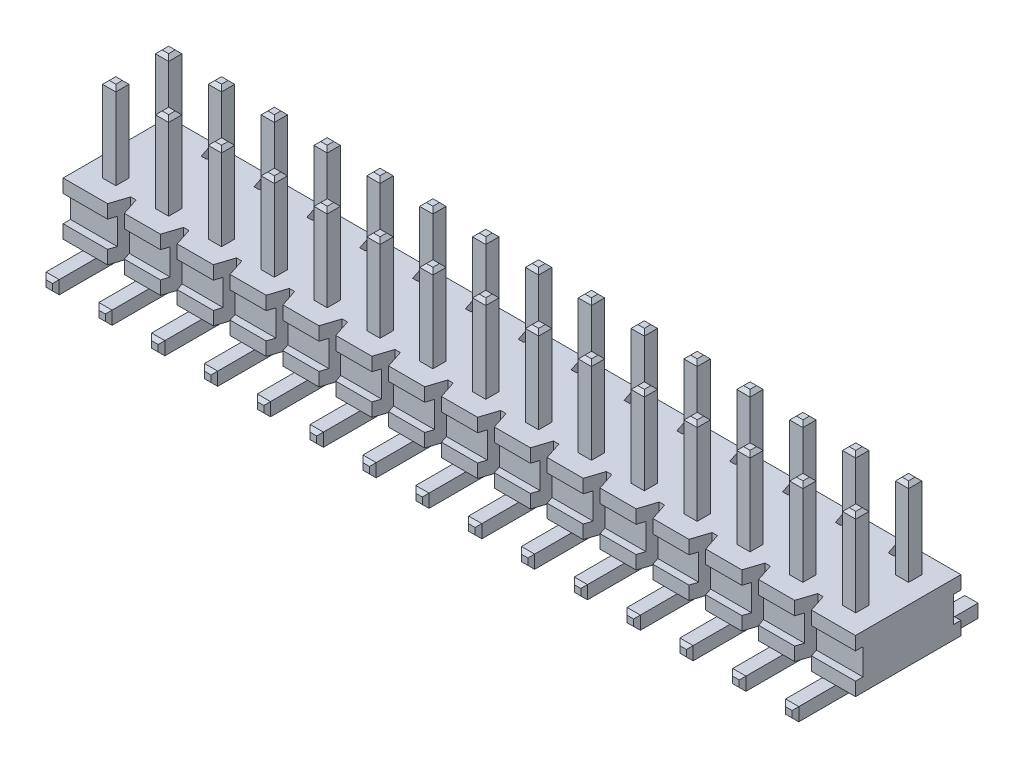
SolidWorks part; units mm, degrees
ref_plane "Front Plane" through (0, 0, 0) normal (0, 0, 1) x (1, 0, 0)
ref_plane "Top Plane" through (0, 0, 0) normal (0, 1, 0) x (1, 0, 0)
ref_plane "Right Plane" through (0, 0, 0) normal (1, 0, 0) x (0, 0, -1)
sketch "Sketch1" plane through (0, 0, 0) normal (0, 1, 0) x (1, 0, 0)
  line L0 (-14.9924, -1.9939) -> (14.9924, 1.9939) construction
  line L1 (-14.9924, 1.9939) -> (14.9924, 1.9939)
  line L2 (-14.9924, 1.9939) -> (-14.9924, -1.9939)
  line L3 (-14.9924, -1.9939) -> (14.9924, -1.9939)
  line L4 (14.9924, 1.9939) -> (14.9924, -1.9939)
  dimension "D1" = 3.9878
  dimension "D2" = 29.9847
extrude "Body" add sketch "Sketch1" along normal mid plane 2.0066
sketch "Sketch3" plane through (0, 1.0033, 0) normal (0, 1, 0) x (1, 0, 0)
  line L0 (-13.3099, 1.9939) -> (-12.6749, 1.9939)
  line L1 (14.9924, 1.9939) -> (-14.9924, 1.9939) construction
  line L2 (-12.6749, 1.9939) -> (-12.8908, 1.3335)
  line L3 (-12.8908, 1.3335) -> (-13.094, 1.3335)
  line L4 (-13.094, 1.3335) -> (-13.3099, 1.9939)
  line L5 (-12.9924, 1.3335) -> (-12.9924, 1.9939) construction
  line L6 (-14.9924, 1.9939) -> (-14.9924, -1.9939) construction
  line L7 (0, 0) -> (-14.9924, 0) construction
  line L8 (-13.094, -1.3335) -> (-13.3099, -1.9939)
  line L9 (-12.8908, -1.3335) -> (-13.094, -1.3335)
  line L10 (-12.6749, -1.9939) -> (-12.8908, -1.3335)
  line L11 (-13.3099, -1.9939) -> (-12.6749, -1.9939)
  dimension "D1" = 0.635
  dimension "D2" = 0.2032
  dimension "D3" = 0.6604
  dimension "D4" = 2
extrude "In-Between Cores" cut sketch "Sketch3" against normal through all
sketch "Sketch4" plane through (-14.9924, 0, 0) normal (-1, 0, 0) x (0, 0, 1)
  line L0 (-1.9939, 1.0033) -> (-1.9939, -1.0033) construction
  line L1 (-1.9939, 0.4953) -> (-1.7145, 0.4953)
  line L2 (-1.9939, 0.4953) -> (-1.9939, -0.4953)
  line L3 (-1.9939, -0.4953) -> (-1.7145, -0.4953)
  line L4 (-1.7145, 0.4953) -> (-1.7145, -0.4953)
  line L5 (1.9939, 1.0033) -> (1.9939, -1.0033) construction
  line L6 (1.9939, 0.4953) -> (1.7145, 0.4953)
  line L7 (1.9939, 0.4953) -> (1.9939, -0.4953)
  line L8 (1.9939, -0.4953) -> (1.7145, -0.4953)
  line L9 (1.7145, 0.4953) -> (1.7145, -0.4953)
  line L10 (-1.9939, 1.0033) -> (1.9939, 1.0033) construction
  line L11 (-1.9939, -1.0033) -> (1.9939, -1.0033) construction
  dimension "D1" = 0.2794
  dimension "D2" = 0.508
  dimension "D3" = 0.508
extrude "Side Cut" cut sketch "Sketch4" against normal through all
sketch "Sketch5" plane through (0, 1.0033, 0) normal (0, 1, 0) x (1, 0, 0)
  line L0 (-13.9924, -1.2502) -> (-13.9924, -0.7498) construction
  line L1 (-14.2425, -0.7498) -> (-13.7422, -0.7498)
  line L2 (-14.2425, -0.7498) -> (-14.2425, -1.2502)
  line L3 (-14.2425, -1.2502) -> (-13.7422, -1.2502)
  line L4 (-13.7422, -0.7498) -> (-13.7422, -1.2502)
  line L5 (-13.7422, -1) -> (-14.2425, -1) construction
  line L6 (-14.9924, 1.9939) -> (-14.9924, -1.9939) construction
  line L7 (-14.9924, -1.9939) -> (-13.3099, -1.9939) construction
  dimension "D1" = 0.5004
  dimension "D2" = 1
  dimension "D3" = 0.9939
extrude "Contact" add sketch "Sketch5" along normal blind 3.2004
chamfer "Contact Chamfer" distance 0.127 angle 45 4 edges at (-13.9923, 4.2037, 0.7498) (-13.7422, 4.2037, 1) (-13.9923, 4.2037, 1.2502) (-14.2425, 4.2037, 1)
pattern_linear "Contact Pattern" count 15 spacing 2 along (1, 0, 0) count 2 spacing 2 along (0, 0, -1) of "Contact", "Contact Chamfer"
pattern_linear "Inbetween Pattern" count 14 spacing 2 along (1, 0, 0) of "In-Between Cores"
sketch "Sketch7" plane through (0, 0, 0) normal (1, 0, 0) x (0, 0, -1)
  line L0 (-3.175, 6.3373) -> (3.175, 6.3373)
  line L1 (-3.175, 6.3373) -> (-3.175, 5.0673)
  line L2 (-3.175, 5.0673) -> (-2.3876, 5.0673)
  line L3 (-2.0828, 4.7625) -> (-2.0828, 1.3081)
  line L4 (-1.778, 1.0033) -> (-1.7526, 1.0033)
  line L5 (-1.4478, 1.3081) -> (-1.4478, 1.3843)
  line L6 (-1.4478, 1.3843) -> (-1.2192, 1.6129)
  line L7 (-1.2192, 1.6129) -> (-1.2192, 1.9177)
  line L8 (-1.2192, 1.9177) -> (-1.4478, 2.3136)
  line L9 (-1.4478, 2.3136) -> (-1.4478, 4.7625)
  line L10 (-1.143, 5.0673) -> (-0.8763, 5.0673)
  line L11 (-0.5715, 4.7625) -> (-0.5715, 2.3136)
  line L12 (-0.5715, 2.3136) -> (-0.6985, 1.9177)
  line L13 (-0.6985, 1.9177) -> (-0.6985, 1.6129)
  line L14 (-0.6985, 1.6129) -> (-0.5279, 1.3175)
  line L15 (0, 0) -> (0, 6.3373) construction
  line L16 (-1.2192, 1.7653) -> (-2.0828, 1.7653) construction
  line L17 (-1.9939, 1.0033) -> (1.9939, 1.0033) construction
  line L18 (0.6985, 1.6129) -> (0.5279, 1.3175)
  line L19 (0.6985, 1.9177) -> (0.6985, 1.6129)
  line L20 (0.5715, 2.3136) -> (0.6985, 1.9177)
  line L21 (0.5715, 4.7625) -> (0.5715, 2.3136)
  line L22 (1.143, 5.0673) -> (0.8763, 5.0673)
  line L23 (1.4478, 2.3136) -> (1.4478, 4.7625)
  line L24 (1.2192, 1.9177) -> (1.4478, 2.3136)
  line L25 (1.2192, 1.6129) -> (1.2192, 1.9177)
  line L26 (1.4478, 1.3843) -> (1.2192, 1.6129)
  line L27 (1.4478, 1.3081) -> (1.4478, 1.3843)
  line L28 (1.778, 1.0033) -> (1.7526, 1.0033)
  line L29 (2.0828, 4.7625) -> (2.0828, 1.3081)
  line L30 (3.175, 5.0673) -> (2.3876, 5.0673)
  line L31 (3.175, 6.3373) -> (3.175, 5.0673)
  arc A0 (-0.5279, 1.3175) -> (0.5279, 1.3175) centre (0, 1.6223) ccw
  arc A1 (-2.3876, 5.0673) -> (-2.0828, 4.7625) centre (-2.3876, 4.7625) cw
  arc A2 (-2.0828, 1.3081) -> (-1.778, 1.0033) centre (-1.778, 1.3081) ccw
  arc A3 (-1.7526, 1.0033) -> (-1.4478, 1.3081) centre (-1.7526, 1.3081) ccw
  arc A4 (-1.4478, 4.7625) -> (-1.143, 5.0673) centre (-1.143, 4.7625) cw
  arc A5 (-0.8763, 5.0673) -> (-0.5715, 4.7625) centre (-0.8763, 4.7625) cw
  arc A6 (0.8763, 5.0673) -> (0.5715, 4.7625) centre (0.8763, 4.7625) ccw
  arc A7 (1.4478, 4.7625) -> (1.143, 5.0673) centre (1.143, 4.7625) ccw
  arc A8 (1.7526, 1.0033) -> (1.4478, 1.3081) centre (1.7526, 1.3081) cw
  arc A9 (2.0828, 1.3081) -> (1.778, 1.0033) centre (1.778, 1.3081) cw
  arc A10 (2.3876, 5.0673) -> (2.0828, 4.7625) centre (2.3876, 4.7625) ccw
  dimension "D12" = 1.2192
  dimension "D14" = 0.3048
  dimension "D1" = 3.175
  dimension "D2" = 1.0922
  dimension "D3" = 0.635
  dimension "D4" = 0.2286
  dimension "D5" = 1.27
  dimension "D6" = 5.334
  dimension "D7" = 45
  dimension "D8" = 0.3048
  dimension "D9" = 0.762
  dimension "D10" = 0.6985
  dimension "D11" = 0.127
  dimension "D13" = 30
sketch "Sketch6" plane through (-14.2425, 0, 0) normal (-1, 0, 0) x (0, 0, 1)
  line L0 (-1.2502, -1.0033) -> (-3.5179, -1.0033)
  line L1 (-1.9939, -1.0033) -> (1.9939, -1.0033) construction
  line L2 (-3.5179, -1.0033) -> (-3.5179, -1.5037)
  line L3 (-3.5179, -1.5037) -> (-1.2502, -1.5037)
  line L4 (-1.2502, -1.0033) -> (-0.7498, -1.0033)
  line L5 (0, 0) -> (0, -2.839) construction
  line L6 (1.2502, -1.0033) -> (0.7498, -1.0033)
  line L7 (3.5179, -1.5037) -> (1.2502, -1.5037)
  line L8 (3.5179, -1.0033) -> (3.5179, -1.5037)
  line L9 (1.2502, -1.0033) -> (3.5179, -1.0033)
  arc A0 (-1.2502, -1.5037) -> (-0.7498, -1.0033) centre (-1.2502, -1.0033) ccw
  arc A1 (1.2502, -1.5037) -> (0.7498, -1.0033) centre (1.2502, -1.0033) cw
  dimension "D1" = 7.0358
  dimension "D2" = 0.5004
extrude "SM" add sketch "Sketch6" against normal blind 0.5004
chamfer "SM Chamfer" distance 0.127 angle 45 8 edges at (-13.9924, -1.0033, 3.5179) (-13.7422, -1.2535, 3.5179) (-13.9924, -1.5037, 3.5179) (-14.2425, -1.2535, 3.5179) (-13.9923, -1.5037, -3.5179) (-13.7422, -1.2535, -3.5179) (-13.9923, -1.0033, -3.5179) (-14.2425, -1.2535, -3.5179)
pattern_linear "SM Pattern" count 15 spacing 1.999 along (1, 0, 0) of "SM", "SM Chamfer"
sketch "Sketch8" plane through (-14.2425, 0, 0) normal (-1, 0, 0) x (0, 0, 1)
  line L0 (1.2502, -1.0033) -> (1.2502, -1.5227)
  line L1 (-1.9939, -1.0033) -> (1.9939, -1.0033) construction
  line L2 (1.2502, -1.0033) -> (0.7498, -1.0033)
  line L3 (0.7498, -1.0033) -> (0.7498, -1.5227)
  line L4 (-0.7498, -1.0033) -> (-1.2502, -1.0033)
  line L5 (-1.2502, -1.0033) -> (-1.2502, -3.5227)
  line L6 (-0.7498, -1.0033) -> (-0.7498, -3.5227)
  line L7 (1.7506, -2.0231) -> (4.5339, -2.0231)
  line L8 (1.7506, -2.5235) -> (4.5339, -2.5235)
  line L9 (4.5339, -2.5235) -> (4.5339, -2.0231)
  line L10 (-0.2494, -4.0231) -> (4.5339, -4.0231)
  line L11 (-0.2494, -4.5235) -> (4.5339, -4.5235)
  line L12 (4.5339, -4.5235) -> (4.5339, -4.0231)
  line L13 (4.5339, -2.2733) -> (0, -2.2733) construction
  line L14 (4.5339, -4.2733) -> (0, -4.2733) construction
  line L15 (1.9939, -0.4953) -> (1.9939, -1.0033) construction
  line L16 (1, 1.0033) -> (1, -1.0033) construction
  line L17 (0.7498, 1.0033) -> (1.2502, 1.0033) construction
  line L18 (-1, 1.0033) -> (-1, -1.0033) construction
  arc A0 (1.2502, -1.5227) -> (1.7506, -2.0231) centre (1.7506, -1.5227) ccw
  arc A1 (0.7498, -1.5227) -> (1.7506, -2.5235) centre (1.7506, -1.5227) ccw
  arc A2 (-0.7498, -3.5227) -> (-0.2494, -4.0231) centre (-0.2494, -3.5227) ccw
  arc A3 (-1.2502, -3.5227) -> (-0.2494, -4.5235) centre (-0.2494, -3.5227) ccw
  dimension "D1" = 0.5004
  dimension "D2" = 0.5004
  dimension "D7" = 0.5004
  dimension "D3" = 1.27
  dimension "D4" = 2
  dimension "D5" = 0.5004
  dimension "D6" = 2.54
  dimension "D8" = 2
sketch "Sketch10" plane through (-14.2425, 0, 0) normal (-1, 0, 0) x (0, 0, 1)
  line L1 (0.7498, -1.0033) -> (1.2502, -1.0033)
  line L2 (0.7498, -1.0033) -> (0.7498, -3.4671)
  line L3 (0.7498, -3.4671) -> (1.2502, -3.4671)
  line L4 (1.2502, -1.0033) -> (1.2502, -3.4671)
  line L5 (1, -1.0033) -> (1, 1.0033) construction
  line L6 (0.7498, 1.0033) -> (1.2502, 1.0033) construction
  line L7 (-1.9939, -1.0033) -> (1.9939, -1.0033) construction
  dimension "D1" = 0.5004
  dimension "D2" = 2.4638
ref_plane "LC Plane" through (-12.9954, 0, 0) normal (1, 0, 0) x (0, 0, -1)
ref_plane "Shroud Plane" through (0, 4.3307, 0) normal (0, 1, 0) x (-1, 0, 0)
ref_plane "AP Plane" through (-12.9924, 0, 0) normal (-1, 0, 0) x (0, 0, 1)
sketch "Sketch11" plane through (-12.9924, 0, 0) normal (1, 0, 0) x (0, 0, -1)
  line L0 (-0.5461, -0.7493) -> (-0.5461, -2.6543)
  line L1 (-1.9939, -1.0033) -> (1.9939, -1.0033) construction
  line L2 (-0.5461, -2.6543) -> (-0.4191, -2.9083)
  line L3 (1.9939, -1.0033) -> (-1.9939, -1.0033) construction
  line L4 (-0.4191, -2.9083) -> (0, -2.9083)
  line L5 (-0.5461, -0.7493) -> (0, -0.7493)
  line L6 (0, -0.7493) -> (0, -2.9083)
  line L7 (0, -0.7493) -> (0, 0) construction
  dimension "D1" = 0.254
  dimension "D2" = 1.905
  dimension "D3" = 0.254
  dimension "D4" = 0.5461
  dimension "D5" = 0.127
sketch "Sketch12" plane through (-12.9954, 0, 0) normal (1, 0, 0) x (0, 0, -1)
  line L0 (-0.5778, -0.8001) -> (-0.5778, -1.61)
  line L1 (-0.5778, -1.61) -> (-0.7112, -1.61)
  line L2 (-0.7112, -1.61) -> (-0.5778, -1.841)
  line L3 (-0.5778, -1.841) -> (-0.5778, -1.8894)
  line L4 (-0.5778, -1.8894) -> (-0.7112, -1.8894)
  line L5 (-0.7112, -1.8894) -> (-0.3429, -2.5273)
  line L6 (-0.2159, -2.5273) -> (-0.2159, -1.3843)
  line L7 (0, -0.8001) -> (0, -3.5027) construction
  line L8 (-0.5778, -0.8001) -> (0.5778, -0.8001)
  line L9 (-0.3429, -2.5273) -> (-0.2159, -2.5273)
  line L10 (0.3429, -2.5273) -> (0.2159, -2.5273)
  line L11 (0.2159, -2.5273) -> (0.2159, -1.3843)
  line L12 (0.7112, -1.8894) -> (0.3429, -2.5273)
  line L13 (0.5779, -1.8894) -> (0.7112, -1.8894)
  line L14 (0.5779, -1.841) -> (0.5779, -1.8894)
  line L15 (0.7112, -1.61) -> (0.5779, -1.841)
  line L16 (0.5779, -1.61) -> (0.7112, -1.61)
  line L17 (0.5778, -0.8001) -> (0.5779, -1.61)
  line L19 (-1.9939, -1.0033) -> (1.9939, -1.0033) construction
  line L20 (0, -0.8001) -> (0, 0) construction
  line L22 (1.9939, -1.0033) -> (-1.9939, -1.0033) construction
  arc A0 (0.2159, -1.3843) -> (-0.2159, -1.3843) centre (0, -1.3843) ccw
  dimension "D5" = 0.7112
  dimension "D1" = 0.2159
  dimension "D2" = 0.5778
  dimension "D3" = 0.2794
  dimension "D4" = 1.143
  dimension "D6" = 30
  dimension "D7" = 0.127
  dimension "D8" = 1.524
  dimension "D9" = 0.2032
ref_plane "Polarize Start Plane" through (-15.9924, 0, 0) normal (-1, 0, 0) x (0, 0, 1)
ref_plane "Polarize Plane" through (-13.9924, 0, 0) normal (-1, 0, 0) x (0, 0, 1)
sketch "Sketch23" plane through (-13.9924, 0, 0) normal (-1, 0, 0) x (0, 0, 1)
  line L0 (-1.9939, 1.0033) -> (1.9939, 1.0033) construction
  line L1 (0.4859, 1.0033) -> (1.5019, 1.0033)
  line L2 (0.4859, 1.0033) -> (0.4859, 4.4577)
  line L3 (0.4859, 4.4577) -> (1.5019, 4.4577)
  line L4 (1.5019, 1.0033) -> (1.5019, 4.4577)
  line L5 (0.8768, 4.2037) -> (1.1232, 4.2037) construction
  line L6 (0.9939, 4.4577) -> (0.9939, 1.0033) construction
  line L7 (1.9939, 1.0033) -> (1.9939, 0.4953) construction
  dimension "D1" = 1.016
  dimension "D2" = 0.254
  dimension "D3" = 1
sketch "Sketch24" plane through (-13.9924, 0, 0) normal (-1, 0, 0) x (0, 0, 1)
  line L0 (-1.9939, -1.0033) -> (1.9939, -1.0033) construction
  line L1 (-0.254, -1.0033) -> (3.556, -1.0033)
  line L2 (-0.254, -1.0033) -> (-0.254, -1.5042)
  line L3 (-0.254, -1.5042) -> (3.556, -1.5042)
  line L4 (3.556, -1.0033) -> (3.556, -1.5042)
  dimension "D1" = 3.81
  dimension "D2" = 0.254
sketch "Sketch27" plane through (0, 0, 0) normal (0, 0, 1) x (1, 0, 0)
  line L0 (-11.0714, -1.0033) -> (-17.1698, -1.0033)
  line L1 (-17.8024, -0.313) -> (-17.2155, 6.3948)
  line L2 (-17.2155, 6.3948) -> (-15.9503, 6.2841)
  line L3 (-15.9503, 6.2841) -> (-15.9282, 6.5372)
  line L4 (-15.9282, 6.5372) -> (-17.7754, 8.7386)
  line L5 (-11.0714, -1.0033) -> (-11.0714, -2.2733)
  line L6 (-11.0714, -2.2733) -> (-18.0458, -2.2733)
  line L7 (-18.6784, -1.583) -> (-17.7754, 8.7386)
  line L8 (-13.9924, -1.0033) -> (-13.9924, -2.2733) construction
  line L9 (-14.9924, -1.0033) -> (-14.2425, -1.0033) construction
  arc A0 (-17.1698, -1.0033) -> (-17.8024, -0.313) centre (-17.1698, -0.3683) cw
  arc A1 (-18.0458, -2.2733) -> (-18.6784, -1.583) centre (-18.0458, -1.6383) cw
  dimension "D1" = 0.254
  dimension "D3" = 0.635
  dimension "D4" = 0.635
  dimension "D2" = 1.27
  dimension "D5" = 1.27
  dimension "D6" = 7.366
  dimension "D7" = 0.762
  dimension "D8" = 3.81
  dimension "D9" = 6.731
  dimension "D10" = 45
  dimension "D11" = 85
